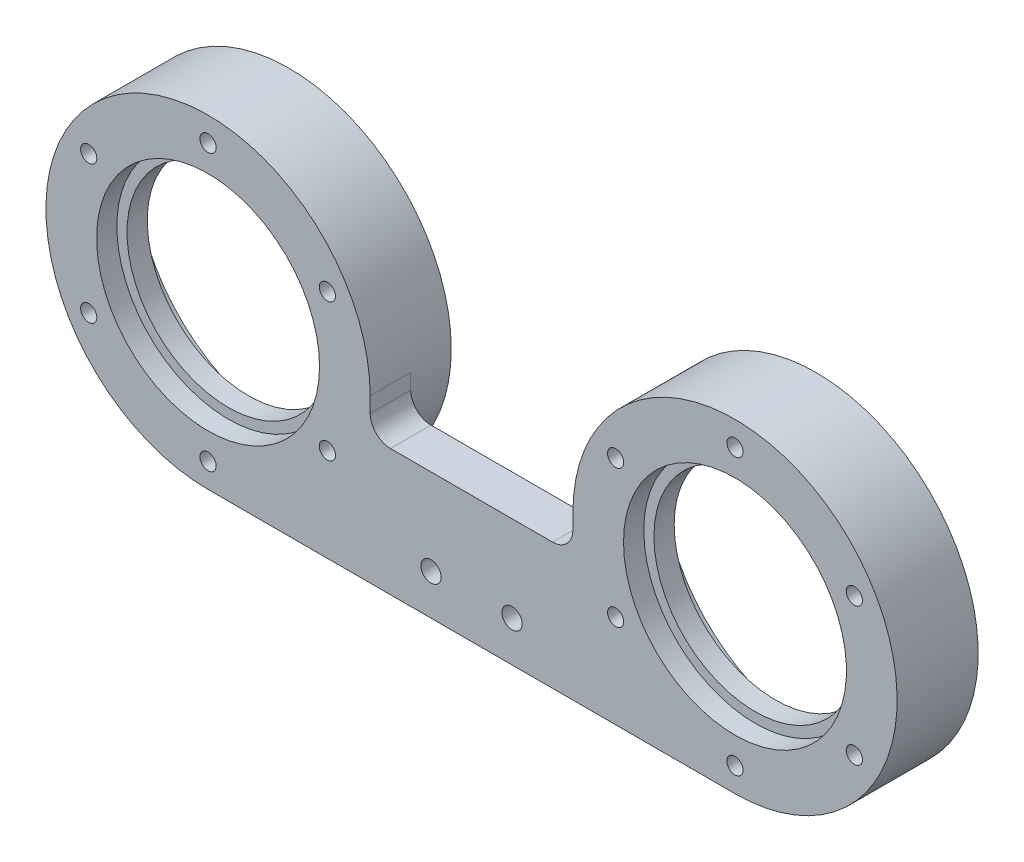
SolidWorks part; units mm, degrees
material "6061 Alloy"
ref_plane "Front Plane" through (0, 0, 0) normal (0, 0, 1) x (1, 0, 0)
ref_plane "Top Plane" through (0, 0, 0) normal (0, 1, 0) x (1, 0, 0)
ref_plane "Right Plane" through (0, 0, 0) normal (1, 0, 0) x (0, 0, -1)
sketch "Sketch1" plane through (0, 0, 0) normal (0, 0, 1) x (1, 0, 0)
  line L0 (0, 0) -> (0, 41.85) construction
  line L2 (0, 0) -> (65, 0) construction
  line L3 (65, 0) -> (65, 40) construction
  line L4 (130, 0) -> (141.6469, 43.4667) construction
  line L5 (130, 0) -> (130, 45) construction
  line L8 (80, 40) -> (80, -40) construction
  line L12 (50, 40) -> (50, -34.2802) construction
  line L19 (0, 40) -> (130, 40)
  line L20 (130, -40) -> (0, -40)
  arc A20 (25, 0) -> (-25, 0) centre (0, 0) ccw
  arc A21 (-25, 0) -> (25, 0) centre (0, 0) ccw
  arc A58 (0, 40) -> (0, -40) centre (0, 0) ccw
  arc A59 (130, 40) -> (130, -40) centre (130, 0) cw
  arc A60 (155, 0) -> (105, 0) centre (130, 0) cw
  arc A61 (105, 0) -> (155, 0) centre (130, 0) cw
  circle A62 centre (0, 0) radius 34 construction
  circle A63 centre (0, 34) radius 2
  circle A64 centre (29.4449, 17) radius 2
  circle A65 centre (29.4449, -17) radius 2
  circle A66 centre (0, -34) radius 2
  circle A67 centre (-29.4449, -17) radius 2
  circle A68 centre (-29.4449, 17) radius 2
  circle A69 centre (130, -34) radius 2
  circle A70 centre (130, 0) radius 34 construction
  circle A71 centre (159.4449, 17) radius 2
  circle A72 centre (159.4449, -17) radius 2
  circle A73 centre (100.5551, -17) radius 2
  circle A74 centre (100.5551, 17) radius 2
  circle A75 centre (130, 34) radius 2
  circle A76 centre (55, 30) radius 2.5
  circle A77 centre (75, 30) radius 2.5
  circle A78 centre (75, -30) radius 2.5
  circle A79 centre (55, -30) radius 2.5
  point P18 (0, 0)
  point P30 (130, 0)
  point P113 (65, -40)
  point P118 (65, -40)
  point P119 (65, -40)
  point P120 (65, -40)
  dimension "D1" = 25
  dimension "D2" = 80
  dimension "D3" = 4
  dimension "D7" = 80
  dimension "D6" = 10
  dimension "D9" = 5
  dimension "D4" = 6
  dimension "D5" = 65
  dimension "D8" = 10
extrude "Boss-Extrude1" add sketch "Sketch1" along normal mid plane 10
sketch "Sketch2" plane through (0, 0, -5) normal (0, 0, -1) x (-1, 0, 0)
  line L0 (-65, -40) -> (-65, 40) construction
  line L1 (-130, 0) -> (-130, 34) construction
  line L2 (0, 0) -> (29, 0) construction
  line L3 (0, 0) -> (0, 34) construction
  line L4 (-130, 0) -> (-159, 0) construction
  line L5 (-130, 25) -> (-130, -25) construction
  circle A5 centre (-130, 0) radius 34 construction
  circle A8 centre (-130, 34) radius 3
  circle A26 centre (-100.5551, 17) radius 3
  circle A27 centre (-100.5551, -17) radius 3
  circle A28 centre (-130, -34) radius 3
  circle A29 centre (-159.4449, -17) radius 3
  circle A30 centre (-159.4449, 17) radius 3
  circle A31 centre (0, 0) radius 34 construction
  circle A32 centre (29.4449, 17) radius 3
  circle A33 centre (29.4449, -17) radius 3
  circle A34 centre (0, -34) radius 3
  circle A35 centre (-29.4449, -17) radius 3
  circle A36 centre (-29.4449, 17) radius 3
  circle A37 centre (0, 34) radius 3
  circle A38 centre (-130, 0) radius 25 construction
  point P19 (-130, 0)
  point P34 (0, 0)
  point P35 (-130, 0)
  dimension "D1" = 68
  dimension "D2" = 6
extrude "Cut-Extrude2" cut sketch "Sketch2" against normal blind 5
ref_plane "Plane1" through (100, 0, 0) normal (1, 0, 0) x (0, 0, -1)
sketch "Sketch6" plane through (0, 0, -5) normal (0, 0, 1) x (1, 0, 0)
  line L0 (65, 40) -> (65, -40) construction
  circle A0 centre (0, 0) radius 38
  circle A1 centre (0, 0) radius 40
  circle A3 centre (130, 0) radius 40
  circle A4 centre (130, 0) radius 38
  arc A5 (0, 40) -> (0, -40) centre (0, 0) ccw construction
  dimension "D1" = 76
extrude "Boss-Extrude2" add sketch "Sketch6" against normal blind 10
sketch "Sketch7" plane through (0, 0, 5) normal (0, 0, 1) x (1, 0, 0)
  line L0 (40, 0) -> (85.2786, 0) construction
  line L5 (0, 52.8) -> (130, 52.8)
  line L6 (0, 40) -> (0, 52.8)
  line L7 (40, 0) -> (40, -8.75)
  line L8 (40, -8.75) -> (90, -8.75)
  line L10 (130, 0) -> (93.6935, 0) construction
  line L11 (0, 0) -> (130, 0) construction
  line L12 (130, 0) -> (65, 0) construction
  line L13 (65, 0) -> (65, 40) construction
  line L14 (130, 40) -> (0, 40) construction
  line L15 (65, 40) -> (65, 60.8745) construction
  line L16 (65, 0) -> (65, -44.4069) construction
  line L17 (90, 0) -> (44.7214, 0) construction
  line L18 (90, 0) -> (90, -8.75)
  line L19 (130, 40) -> (130, 52.8)
  arc A0 (40, 0) -> (0, 40) centre (0, 0) ccw
  arc A2 (90, 0) -> (130, 40) centre (130, 0) cw
  point P24 (65, -8.75)
  point P25 (65, 52.8)
  dimension "D1" = 17.5
extrude "Cut-Extrude3" cut sketch "Sketch7" against normal blind 29
fillet "Fillet1" radius 5 2 edges at (40, -8.75, 0) (90, -8.75, 0)
sketch "Sketch8" plane through (0, 0, 5) normal (0, 0, 1) x (1, 0, 0)
  line L0 (65, -8.75) -> (65, -40) construction
  line L1 (45, -8.75) -> (85, -8.75) construction
  line L2 (0, -40) -> (130, -40) construction
  circle A0 centre (0, 0) radius 27.5
  circle A1 centre (130, 0) radius 27.5
  dimension "D1" = 55
extrude "Cut-Extrude4" cut sketch "Sketch8" against normal blind 5
equation "\"c\"=6.25"
